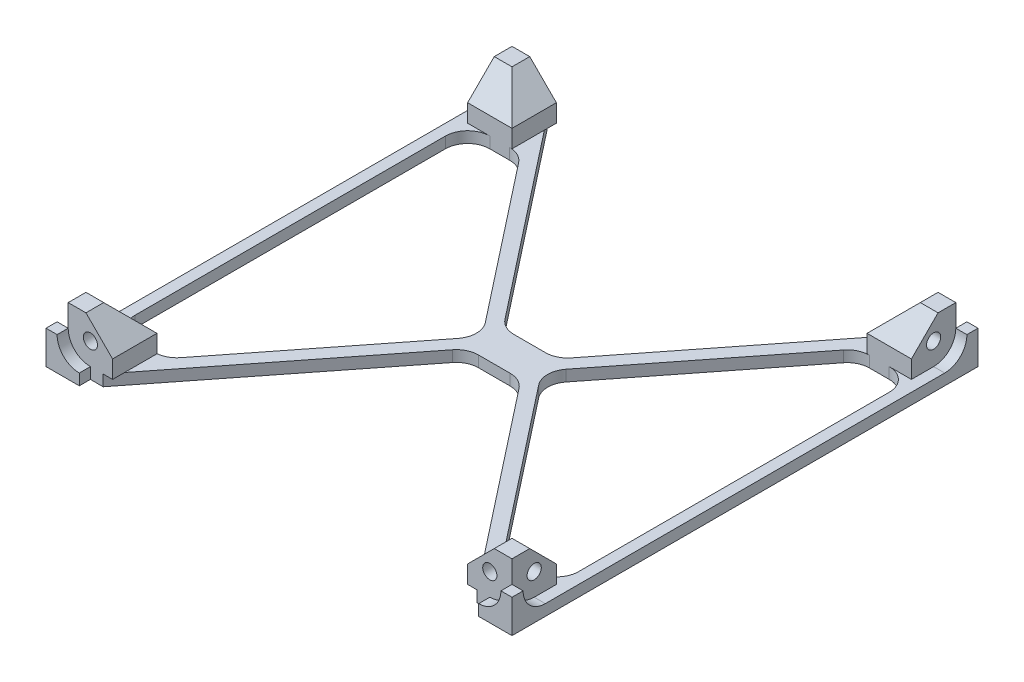
SolidWorks part; units mm, degrees
ref_plane "Front Plane" through (0, 0, 0) normal (0, 0, 1) x (1, 0, 0)
ref_plane "Top Plane" through (0, 0, 0) normal (0, 1, 0) x (1, 0, 0)
ref_plane "Right Plane" through (0, 0, 0) normal (1, 0, 0) x (0, 0, -1)
ref_axis "Axis1" through (0, 13.125, 0) along (0, -1, 0)
sketch "Sketch1" plane through (0, 0, 0) normal (0, 1, 0) x (1, 0, 0)
  line L989 (-45, 45) -> (45, 45) construction
  line L1008 (-52.5, -52.5) -> (52.5, -52.5) construction
  line L1009 (-52.5, -52.5) -> (-52.5, 52.5) construction
  line L1028 (-52.5, 52.5) -> (52.5, 52.5) construction
  line L1029 (52.5, -52.5) -> (52.5, 52.5) construction
  line L1030 (-52.5, -52.5) -> (52.5, 52.5) construction
  line L1031 (-52.5, 52.5) -> (52.5, -52.5) construction
  line L1032 (45, 45) -> (45, -45) construction
  line L1033 (45, -45) -> (-45, -45) construction
  line L1034 (-45, -45) -> (-45, 45) construction
  line L1035 (-52.5, 45) -> (-52.5, -45)
  line L1037 (-50, 40) -> (-50, -40)
  line L1038 (-52.5, 0) -> (-50, 0) construction
  line L1040 (-42.1272, 50) -> (-6, 4)
  line L1041 (-6, 4) -> (6, 4)
  line L1042 (-38.088, 40) -> (-6.6731, 0)
  line L1043 (-32.12, 32.401) -> (-29.7607, 34.254) construction
  line L1044 (-50, 40) -> (-38.088, 40)
  line L1045 (-6.6731, 0) -> (0, 0) construction
  line L1046 (-55, 0) -> (55, 0) construction
  line L1047 (-50, -40) -> (-38.088, -40)
  line L1048 (-6, -4) -> (6, -4)
  line L1049 (-42.1272, -50) -> (-6, -4)
  line L1050 (-38.088, -40) -> (-6.6731, 0)
  line L1053 (0, -55) -> (0, 55) construction
  line L1056 (50, -40) -> (38.088, -40)
  line L1057 (38.088, -40) -> (6.6731, 0)
  line L1058 (42.1272, -50) -> (6, -4)
  line L1059 (38.088, 40) -> (6.6731, 0)
  line L1060 (42.1272, 50) -> (6, 4)
  line L1061 (45, 50) -> (42.1272, 50)
  line L1063 (50, 40) -> (38.088, 40)
  line L1064 (50, 40) -> (50, -40)
  line L1065 (52.5, 45) -> (52.5, -45)
  line L1066 (-52.5, 45) -> (-52.5, 52.5)
  line L1068 (-52.5, -45) -> (-52.5, -52.5)
  line L1071 (52.5, -52.5) -> (52.5, -45)
  line L1073 (52.5, 52.5) -> (52.5, 45)
  line L1074 (-52.5, 52.5) -> (-45, 52.5)
  line L1075 (-45, 52.5) -> (-45, 50)
  line L1076 (-45, 50) -> (-42.1272, 50)
  line L1077 (-52.5, -52.5) -> (-45, -52.5)
  line L1078 (-45, -52.5) -> (-45, -50)
  line L1079 (-45, -50) -> (-42.1272, -50)
  line L1080 (52.5, -52.5) -> (45, -52.5)
  line L1081 (45, -52.5) -> (45, -50)
  line L1082 (45, -50) -> (42.1272, -50)
  line L1083 (45, 50) -> (45, 52.5)
  line L1084 (45, 52.5) -> (52.5, 52.5)
  circle A11 centre (-45, 45) radius 1.625
  circle A12 centre (45, 45) radius 1.625
  circle A13 centre (45, -45) radius 1.625
  circle A14 centre (-45, -45) radius 1.625
  point P0 (0, 0)
  dimension "D5" = 2.5
  dimension "D6" = 3
  dimension "D8" = 12
  dimension "D7" = 5
  dimension "D2" = 90
  dimension "D3" = 3.25
  dimension "D1" = 105
  dimension "D9" = 8
extrude "Boss-Extrude1" add sketch "Sketch1" along normal blind 2.5
fillet "Fillet1" radius 5 6 edges at (6, 1.25, 4) (-6, 1.25, 4) (6, 1.25, -4) (-6, 1.25, -4) (6.6731, 1.25, 0) (-6.6731, 1.25, 0)
fillet "Fillet2" radius 5 8 edges at (50, 1.25, -40) (38.088, 1.25, -40) (38.088, 1.25, 40) (50, 1.25, 40) (-38.088, 1.25, 40) (-50, 1.25, 40) (-38.088, 1.25, -40) (-50, 1.25, -40)
chamfer "Chamfer2" distance 1.6 angle 45 4 edges at (45, 0, 46.625) (45, 0, -43.375) (-45, 0, 46.625) (-45, 0, -43.375)
sketch "Sketch2" plane through (0, 2.5, 0) normal (0, 1, 0) x (1, 0, 0)
  line L1 (-50, 40) -> (-40, 40)
  line L2 (-50, 40) -> (-50, 50)
  line L3 (-50, 50) -> (-40, 50)
  line L4 (-40, 40) -> (-40, 50)
  line L5 (-50, 40) -> (-40, 50) construction
  line L6 (-50, 50) -> (-40, 40) construction
  point P0 (-45, 45)
  dimension "D1" = 10
extrude "Boss-Extrude2" add sketch "Sketch2" along normal blind 10
sketch "Sketch3" plane through (-50, 0, 0) normal (-1, 0, 0) x (0, 0, 1)
  line L0 (-50, 12.5) -> (-40, 2.5) construction
  circle A0 centre (-45, 7.5) radius 1.6
  dimension "D1" = 3.2
extrude "Cut-Extrude1" cut sketch "Sketch3" against normal blind 3.2
sketch "Sketch4" plane through (0, 0, -50) normal (0, 0, -1) x (-1, 0, 0)
  line L0 (40, 12.5) -> (50, 2.5) construction
  circle A0 centre (45, 7.5) radius 1.6
  dimension "D1" = 3.2
extrude "Cut-Extrude2" cut sketch "Sketch4" against normal blind 3.2
chamfer "Chamfer1" distance 6 angle 45 2 edges at (-40, 12.5, -45) (-45, 12.5, -40)
sketch "Sketch5" plane through (0, 2.5, 0) normal (0, 1, 0) x (1, 0, 0)
  line L0 (-45, 50) -> (-45, 52.5)
  line L1 (-45, 52.5) -> (-52.5, 52.5)
  line L2 (-52.5, 52.5) -> (-52.5, 45)
  line L3 (-52.5, 52.5) -> (-52.5, -52.5) construction
  line L4 (-52.5, 45) -> (-50, 45)
  line L5 (-50, 50) -> (-50, 40) construction
  line L6 (-50, 45) -> (-50, 50)
  line L7 (-50, 50) -> (-45, 50)
extrude "Boss-Extrude3" add sketch "Sketch5" along normal blind 5
pattern_circular "CirPattern1" count 4 over 360 about axis through (0, 13.125, 0) along (0, -1, 0) of "Boss-Extrude2", "Cut-Extrude1", "Cut-Extrude2", "Chamfer1", "Boss-Extrude3"
sketch "Sketch7" plane through (0, 0, -52.5) normal (0, 0, -1) x (-1, 0, 0)
  circle A0 centre (45, 7.5) radius 5
  circle A1 centre (-45, 7.5) radius 5
  dimension "D1" = 10
sketch "Sketch6" plane through (-52.5, 0, 0) normal (-1, 0, 0) x (0, 0, 1)
  circle A0 centre (-45, 7.5) radius 5
  circle A1 centre (45, 7.5) radius 5
  dimension "D1" = 10
extrude "Cut-Extrude5" cut sketch "Sketch7" against normal up to surface (2.5 mm away) up to face at (44.4923, 5.9331, -50)
extrude "Cut-Extrude6" cut sketch "Sketch6" against normal up to surface (2.5 mm away) up to face at (-50, 7.4164, -45.0836)
sketch "Sketch8" plane through (0, 0, 52.5) normal (0, 0, 1) x (1, 0, 0)
  circle A0 centre (-45, 7.5) radius 5
  circle A1 centre (45, 7.5) radius 5
  dimension "D1" = 10
extrude "Cut-Extrude7" cut sketch "Sketch8" against normal up to surface (2.5 mm away) up to face at (-44.4923, 5.9331, 50)
sketch "Sketch9" plane through (52.5, 0, 0) normal (1, 0, 0) x (0, 0, -1)
  circle A0 centre (-45, 7.5) radius 5
  circle A1 centre (45, 7.5) radius 5
  dimension "D1" = 10
extrude "Cut-Extrude8" cut sketch "Sketch9" against normal up to surface (2.5 mm away) up to face at (50, 7.4164, 45.0836)
